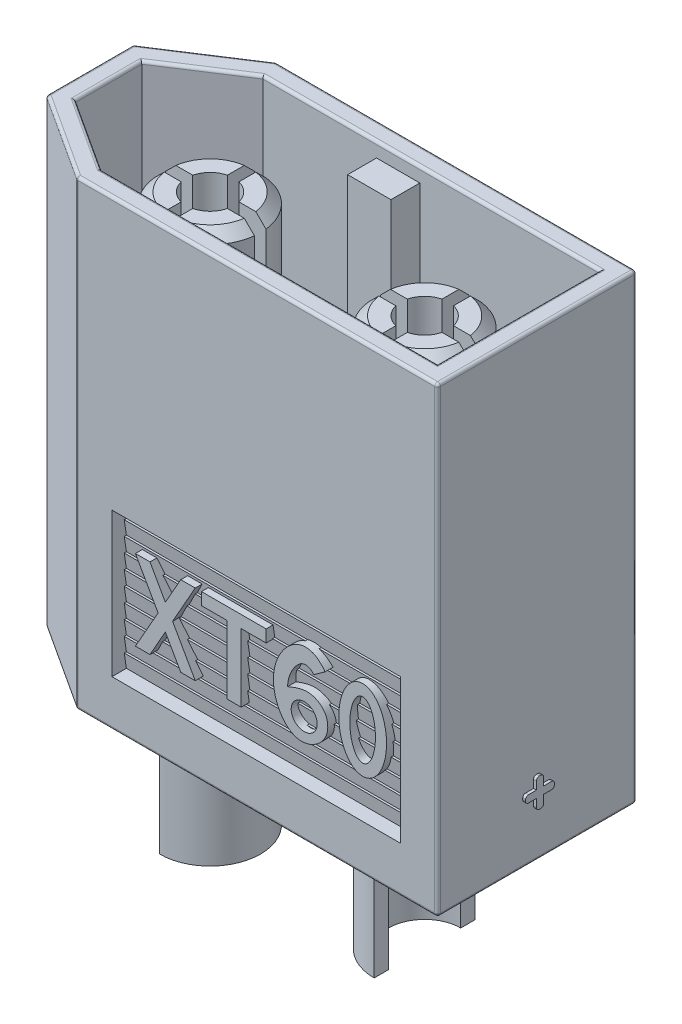
SolidWorks part; units mm, degrees
material "PMMA"
ref_plane "Front Plane" through (0, 0, 0) normal (0, 0, 1) x (1, 0, 0)
ref_plane "Top Plane" through (0, 0, 0) normal (0, 1, 0) x (1, 0, 0)
ref_plane "Right Plane" through (0, 0, 0) normal (1, 0, 0) x (0, 0, -1)
sketch "Sketch1" plane through (0, 0, 0) normal (0, 1, 0) x (1, 0, 0)
  line L1 (-158.75, 87.63) -> (158.75, 87.63)
  line L3 (-158.75, -87.63) -> (158.75, -87.63)
  line L4 (158.75, 87.63) -> (158.75, -87.63)
  line L5 (-158.75, 87.63) -> (158.75, -87.63) construction
  line L6 (-158.75, -87.63) -> (158.75, 87.63) construction
  line L7 (-234.95, 38.1) -> (-234.95, -38.1)
  line L8 (-234.95, 38.1) -> (-158.75, 87.63)
  line L9 (-234.95, -38.1) -> (-158.75, -87.63)
  point P0 (0, 0)
  point P11 (-234.95, 0)
  dimension "D1" = 317.5
  dimension "D2" = 175.26
  dimension "D3" = 76.2
  dimension "D4" = 76.2
  dimension "D5" = 76.2
extrude "Boss-Extrude1" add sketch "Sketch1" along normal blind 406.4
sketch "Sketch4" plane through (0, 406.4, 0) normal (0, 1, 0) x (1, 0, 0)
  line L12 (142.24, -71.12) -> (142.24, 71.12)
  line L13 (142.24, 71.12) -> (-153.8558, 71.12)
  line L14 (-153.8558, 71.12) -> (-218.44, 29.1403)
  line L15 (-218.44, 29.1403) -> (-218.44, -29.1403)
  line L16 (-218.44, -29.1403) -> (-153.8558, -71.12)
  line L17 (-153.8558, -71.12) -> (142.24, -71.12)
  line L18 (142.24, -71.12) -> (142.24, 71.12)
  line L19 (142.24, 71.12) -> (-153.8558, 71.12)
  line L20 (-153.8558, 71.12) -> (-218.44, 29.1403)
  line L21 (-218.44, 29.1403) -> (-218.44, -29.1403)
  line L22 (-218.44, -29.1403) -> (-153.8558, -71.12)
  line L23 (-153.8558, -71.12) -> (142.24, -71.12)
  dimension "D1" = 16.51
extrude "Cut-Extrude2" cut sketch "Sketch4" against normal blind 215.9
sketch "Sketch5" plane through (0, 0, 0) normal (0, -1, 0) x (1, 0, 0)
  circle A0 centre (-129.1768, 0) radius 69.85
  circle A1 centre (59.7244, 0) radius 69.85
extrude "Cut-Extrude3" cut sketch "Sketch5" against normal blind 76.2
sketch "Sketch6" plane through (0, 76.2, 0) normal (0, -1, 0) x (1, 0, 0)
  circle A0 centre (-129.1768, 0) radius 47.625
  circle A1 centre (59.7244, 0) radius 47.625
extrude "Boss-Extrude2" add sketch "Sketch6" along normal blind 2.54 and the other way blind 121.92 contours A0 | A1
sketch "Sketch7" plane through (0, 73.66, 0) normal (0, -1, 0) x (1, 0, 0)
  circle A0 centre (-129.1768, 0) radius 44.45
  circle A1 centre (59.7244, 0) radius 44.45
extrude "Boss-Extrude3" add sketch "Sketch7" along normal blind 190.5 and the other way blind 292.1
chamfer "Chamfer2" distance 6.35 angle 50 2 edges at (-129.1768, 198.12, -47.625) (59.7244, 198.12, -47.625) first distance on face at (-129.1768, 198.12, -44.45) first distance on face at (59.7244, 198.12, -44.45)
sketch "Sketch8" plane through (0, -116.84, 0) normal (0, -1, 0) x (1, 0, 0)
  line L0 (59.7244, -44.45) -> (59.7244, -31.75)
  line L1 (-129.1768, -44.45) -> (-129.1768, -31.75)
  line L2 (59.7244, 31.75) -> (59.7244, 44.45)
  line L3 (-129.1768, 31.75) -> (-129.1768, 44.45)
  arc A0 (59.7244, 31.75) -> (59.7244, -31.75) centre (59.7244, 0) ccw
  circle A1 centre (59.7244, 0) radius 44.45
  arc A2 (59.7244, -44.45) -> (59.7244, 44.45) centre (59.7244, 0) ccw
  circle A3 centre (-129.1768, 0) radius 44.45
  arc A4 (-129.1768, 44.45) -> (-129.1768, -44.45) centre (-129.1768, 0) ccw
  arc A5 (-129.1768, -31.75) -> (-129.1768, 31.75) centre (-129.1768, 0) ccw
  point P11 (59.7244, 0)
  point P14 (-129.1768, 0)
  dimension "D1" = 0
  dimension "D2" = 0
extrude "Cut-Extrude4" cut sketch "Sketch8" against normal blind 95.25
sketch "Sketch9" plane through (0, -21.59, 0) normal (0, -1, 0) x (1, 0, 0)
  circle A0 centre (-129.1768, 0) radius 31.75
  circle A1 centre (59.7244, 0) radius 31.75
extrude "Cut-Extrude5" cut sketch "Sketch9" against normal blind 170.942
sketch "Sketch10" plane through (0, 365.76, 0) normal (0, 1, 0) x (1, 0, 0)
  circle A0 centre (-129.1768, 0) radius 20.955
  circle A1 centre (59.7244, 0) radius 20.955
extrude "Cut-Extrude6" cut sketch "Sketch10" against normal blind 610.362
fillet "Chamfer3" radius 8.89 1 edges at (-129.1768, 365.76, -44.45) type face fillet profile chamfer first side face at (-129.1768, 194.3362, -44.45) second side face at (-129.1768, 365.76, 20.955)
fillet "Chamfer4" radius 8.89 1 edges at (59.7244, 365.76, -44.45) type face fillet profile chamfer first side face at (59.7244, 194.3362, -44.45) second side face at (59.7244, 365.76, 20.955)
sketch "Sketch12" plane through (0, 365.76, 0) normal (0, 1, 0) x (1, 0, 0)
  line L0 (64.8044, -5.08) -> (120.481, -5.08)
  line L1 (-188.1008, 5.08) -> (-134.2568, 5.08)
  line L2 (-188.1008, 5.08) -> (-188.1008, -5.08)
  line L3 (-188.1008, -5.08) -> (-134.2568, -5.08)
  line L4 (-70.2527, 5.08) -> (-70.2527, -5.08)
  line L5 (54.6444, -5.08) -> (54.6444, -61.0793)
  line L6 (64.8044, 5.08) -> (120.481, 5.08)
  line L7 (-134.2568, 61.0793) -> (-124.0968, 61.0793)
  line L8 (-134.2568, 61.0793) -> (-134.2568, 5.08)
  line L9 (-134.2568, -61.0793) -> (-124.0968, -61.0793)
  line L10 (-124.0968, 61.0793) -> (-124.0968, 5.08)
  line L11 (64.8044, -5.08) -> (64.8044, -61.0793)
  line L12 (-124.0968, -5.08) -> (-70.2527, -5.08)
  line L13 (54.6444, 61.0793) -> (64.8044, 61.0793)
  line L14 (54.6444, 61.0793) -> (54.6444, 5.08)
  line L15 (54.6444, -61.0793) -> (64.8044, -61.0793)
  line L16 (64.8044, 61.0793) -> (64.8044, 5.08)
  line L17 (-134.2568, -5.08) -> (-134.2568, -61.0793)
  line L18 (-124.0968, 5.08) -> (-70.2527, 5.08)
  line L19 (-1.0323, 5.08) -> (54.6444, 5.08)
  line L20 (-1.0323, 5.08) -> (-1.0323, -5.08)
  line L21 (-1.0323, -5.08) -> (54.6444, -5.08)
  line L22 (120.481, 5.08) -> (120.481, -5.08)
  line L23 (-124.0968, -5.08) -> (-124.0968, -61.0793)
  point P0 (-129.1768, 0)
  point P6 (-129.1768, 0)
  point P11 (59.7244, 0)
  point P17 (59.7244, 0)
  dimension "D1" = 10.16
  dimension "D2" = 10.16
  dimension "D3" = 10.16
  dimension "D4" = 10.16
extrude "Cut-Extrude7" cut sketch "Sketch12" against normal blind 127
sketch "Sketch13" plane through (0, 190.5, 0) normal (0, 1, 0) x (1, 0, 0)
  line L0 (-81.5518, 0) -> (12.0994, 0)
  line L1 (-153.8558, -71.12) -> (142.24, -71.12) construction
  line L2 (-53.7762, 71.12) -> (-15.6762, 71.12)
  line L3 (-53.7762, 71.12) -> (-53.7762, -71.12)
  line L4 (-53.7762, -71.12) -> (-15.6762, -71.12)
  line L5 (-15.6762, 71.12) -> (-15.6762, -71.12)
  line L6 (-53.7762, 71.12) -> (-15.6762, -71.12) construction
  line L7 (-53.7762, -71.12) -> (-15.6762, 71.12) construction
  circle A0 centre (-129.1768, 0) radius 47.625 construction
  circle A1 centre (59.7244, 0) radius 47.625 construction
  point P7 (-34.7262, 0)
  dimension "D1" = 38.1
extrude "Cut-Extrude8" cut sketch "Sketch13" against normal blind 43.18 contours L3 L4 L5 L2
sketch "Sketch14" plane through (0, 147.32, 0) normal (0, 1, 0) x (1, 0, 0)
  line L0 (-15.6762, 71.12) -> (-15.6762, -71.12) construction
  line L1 (-53.7762, 71.12) -> (-15.6762, 71.12)
  line L2 (-53.7762, 71.12) -> (-53.7762, 45.72)
  line L3 (-53.7762, 45.72) -> (-15.6762, 45.72)
  line L4 (-15.6762, 71.12) -> (-15.6762, 45.72)
  dimension "D1" = 25.4
extrude "Boss-Extrude4" add sketch "Sketch14" along normal blind 246.38
fillet "Fillet1" radius 2.54 24 edges at (158.75, 406.4, 0) (142.24, 406.4, 0) (-5.8079, 406.4, -71.12) (-186.1479, 406.4, -50.1301) (-218.44, 406.4, 0) (-186.1479, 406.4, 50.1301) (-5.8079, 406.4, 71.12) (0, 406.4, 87.63) (0, 406.4, -87.63) (-196.85, 406.4, -62.865) (-234.95, 406.4, 0) (-196.85, 406.4, 62.865) (-196.85, 0, -62.865) (-234.95, 0, 0) (-196.85, 0, 62.865) (0, 0, 87.63) (158.75, 0, 0) (0, 0, -87.63) (158.75, 203.2, 87.63) (-158.75, 203.2, 87.63) (-234.95, 203.2, 38.1) (-234.95, 203.2, -38.1) (-158.75, 203.2, -87.63) (158.75, 203.2, -87.63)
sketch "Sketch15" plane through (158.75, 0, 0) normal (1, 0, 0) x (0, 0, -1)
  line L0 (3.175, 56.515) -> (12.7, 56.515)
  line L2 (-3.175, 50.165) -> (-3.175, 40.64)
  line L3 (-12.7, 56.515) -> (-3.175, 56.515)
  line L4 (-12.7, 56.515) -> (-12.7, 50.165)
  line L5 (-12.7, 50.165) -> (-3.175, 50.165)
  line L6 (12.7, 56.515) -> (12.7, 50.165)
  line L7 (3.175, 50.165) -> (3.175, 40.64)
  line L8 (3.175, 50.165) -> (12.7, 50.165)
  line L9 (3.175, 66.04) -> (-3.175, 66.04)
  line L10 (3.175, 66.04) -> (3.175, 56.515)
  line L11 (3.175, 40.64) -> (-3.175, 40.64)
  line L12 (-3.175, 66.04) -> (-3.175, 56.515)
extrude "Boss-Extrude5" add sketch "Sketch15" along normal blind 2.54
fillet "Fillet3" radius 2.54 8 edges at (160.02, 66.04, 3.175) (160.02, 56.515, 12.7) (160.02, 50.165, 12.7) (160.02, 40.64, 3.175) (160.02, 40.64, -3.175) (160.02, 50.165, -12.7) (160.02, 56.515, -12.7) (160.02, 66.04, -3.175)
sketch "Sketch16" plane through (-234.95, 0, 0) normal (-1, 0, 0) x (0, 0, 1)
  line L3 (-12.7, 56.515) -> (12.7, 56.515)
  line L4 (-12.7, 56.515) -> (-12.7, 50.165)
  line L5 (-12.7, 50.165) -> (12.7, 50.165)
  line L6 (12.7, 56.515) -> (12.7, 50.165)
  line L7 (-12.7, 56.515) -> (12.7, 50.165) construction
  line L8 (-12.7, 50.165) -> (12.7, 56.515) construction
extrude "Boss-Extrude6" add sketch "Sketch16" along normal blind 2.54
fillet "Fillet4" radius 2.54 4 edges at (-236.22, 50.165, -12.7) (-236.22, 56.515, -12.7) (-236.22, 50.165, 12.7) (-236.22, 56.515, 12.7)
sketch "Sketch17" plane through (0, 0, -87.63) normal (0, 0, -1) x (-1, 0, 0)
  line L0 (0.8935, 2.54) -> (0.8935, 104.14)
  line L1 (-156.21, 2.54) -> (157.997, 2.54) construction
  line L3 (127.8935, 167.64) -> (-126.1065, 167.64)
  line L4 (127.8935, 167.64) -> (127.8935, 40.64)
  line L5 (127.8935, 40.64) -> (-126.1065, 40.64)
  line L6 (-126.1065, 167.64) -> (-126.1065, 40.64)
  line L7 (127.8935, 167.64) -> (-126.1065, 40.64) construction
  line L8 (127.8935, 40.64) -> (-126.1065, 167.64) construction
  dimension "D1" = 101.6
  dimension "D2" = 254
  dimension "D3" = 127
extrude "Cut-Extrude9" cut sketch "Sketch17" against normal blind 12.7 contours L3 L6 L5 L4 region at (-125.0537, 104.14, -87.63)
sketch "Sketch18" plane through (0, 0, 87.63) normal (0, 0, 1) x (1, 0, 0)
  line L4 (126.1065, 167.64) -> (-127.8935, 167.64)
  line L5 (126.1065, 40.64) -> (126.1065, 167.64)
  line L6 (-127.8935, 40.64) -> (126.1065, 40.64)
  line L7 (-127.8935, 167.64) -> (-127.8935, 40.64)
  line L8 (126.1065, 167.64) -> (-127.8935, 167.64)
  line L9 (126.1065, 40.64) -> (126.1065, 167.64)
  line L10 (-127.8935, 40.64) -> (126.1065, 40.64)
  line L11 (-127.8935, 167.64) -> (-127.8935, 40.64)
  dimension "D1" = 0
extrude "Cut-Extrude10" cut sketch "Sketch18" against normal blind 12.7
sketch "Sketch20" plane through (126.1065, 0, 0) normal (-1, 0, 0) x (0, 0, 1)
  line L0 (-76.835, 167.64) -> (-74.93, 154.94)
  line L1 (-74.93, 167.64) -> (-76.835, 167.64)
  line L5 (-74.93, 154.94) -> (-76.835, 154.94)
  line L6 (-76.835, 154.94) -> (-74.93, 142.24)
  line L7 (-74.93, 142.24) -> (-76.835, 142.24)
  line L8 (-76.835, 142.24) -> (-74.93, 129.54)
  line L9 (-74.93, 129.54) -> (-76.835, 129.54)
  line L10 (-76.835, 129.54) -> (-74.93, 116.84)
  line L11 (-74.93, 116.84) -> (-76.835, 116.84)
  line L12 (-76.835, 116.84) -> (-74.93, 104.14)
  line L13 (-74.93, 104.14) -> (-76.835, 104.14)
  line L14 (-76.835, 104.14) -> (-74.93, 91.44)
  line L15 (-74.93, 91.44) -> (-76.835, 91.44)
  line L16 (-76.835, 91.44) -> (-74.93, 78.74)
  line L17 (-74.93, 78.74) -> (-76.835, 78.74)
  line L18 (-76.835, 78.74) -> (-74.93, 66.04)
  line L19 (-74.93, 66.04) -> (-76.835, 66.04)
  line L20 (-76.835, 66.04) -> (-74.93, 53.34)
  line L21 (-74.93, 53.34) -> (-76.835, 53.34)
  line L22 (-76.835, 53.34) -> (-74.93, 40.64)
  line L24 (-74.93, 167.64) -> (-73.0547, 167.64)
  line L25 (-73.0547, 167.64) -> (-73.0547, 40.64)
  line L26 (-73.0547, 40.64) -> (-74.93, 40.64)
  dimension "D1" = 10
extrude "Boss-Extrude8" add sketch "Sketch20" along normal blind 254
sketch "Sketch24" plane through (0, 0, 74.93) normal (0, 0, 1) x (1, 0, 0)
  line L3 (-112.3337, 69.136) -> (-99.5117, 69.136)
  line L8 (-59.6881, 69.136) -> (-72.3956, 69.136)
  line L9 (-59.6881, 139.7869) -> (-72.3956, 139.7869)
  line L10 (-112.3337, 139.7869) -> (-99.5117, 139.7869)
  line L11 (-99.5117, 139.7869) -> (-85.9731, 115.7681)
  line L12 (-72.3956, 139.7869) -> (-85.9731, 115.7681)
  line L13 (-112.3337, 139.7869) -> (-92.3647, 104.4615)
  line L14 (-59.6881, 139.7869) -> (-79.5999, 104.4615)
  line L15 (-92.3647, 104.4615) -> (-112.3337, 69.136)
  line L16 (-79.5999, 104.4615) -> (-59.6881, 69.136)
  line L18 (-85.9731, 93.1548) -> (-99.5117, 69.136)
  line L19 (-85.9731, 93.1548) -> (-72.3956, 69.136)
  line L20 (-19.2107, 129.0815) -> (2.744, 129.0815)
  line L21 (-19.2107, 139.8309) -> (-31.8277, 139.8309)
  line L22 (-19.2107, 129.0815) -> (-19.2107, 69.18)
  line L23 (-19.2107, 69.18) -> (-31.8277, 69.18)
  line L24 (-31.8277, 129.0815) -> (-31.8277, 69.18)
  line L25 (44.665, 125.9321) -> (54.5941, 133.0073)
  line L27 (-54.2126, 139.8309) -> (2.744, 139.8309)
  line L28 (-54.2126, 139.8309) -> (-54.2126, 129.0815)
  line L29 (-54.2126, 129.0815) -> (-31.8277, 129.0815)
  line L30 (2.744, 139.8309) -> (2.744, 129.0815)
  circle A0 centre (36.2346, 89.7538) radius 11.4519
  ellipse E0 centre (87.7023, 105.3338) end of major axis (87.7023, 69.9643) minor radius 21.0247
  ellipse E1 centre (87.7023, 105.3338) end of major axis (87.7023, 80.0414) minor radius 11.2698
  spline S2 degree 3 poles (54.5941, 133.0073) (36.5453, 158.3364) (-7.5592, 116.0653) (25.4379, 59.9073) (57.7026, 79.0859) (57.8368, 102.2901) (40.1612, 112.982) (28.1928, 107.9257) (21.6829, 105.2817) (21.6192, 105.2555) knots 0 0 0 0 0.346903 0.566821 0.697461 0.793699 0.867755 0.974591 0.975653 0.975653 0.975653 0.975653
  spline S3 degree 3 poles (44.665, 125.9321) (37.8345, 133.7755) (25.8368, 123.8865) (21.7671, 111.0708) (21.6192, 105.2555) knots 0 0 0 0 0.190849 0.355801 0.355801 0.355801 0.355801
  point P6 (-86.0109, 104.4615)
  point P19 (-25.5192, 104.4615)
extrude "Boss-Extrude9" add sketch "Sketch24" along normal blind 7.62 contours L18 L19 L8 L16 L14 L9 L12 L11 L10 L13 L15 L3 | L30 L27 L21 L28 L29 L24 L23 L22 L20 | S3 L25 S2 A0 | E0 E1 region at (-86.015, 104.4615, 74.93) region at (-25.6155, 114.9404, 74.93) region at (31.1425, 105.8846, 74.93) region at (87.6546, 139.8803, 74.93)
mirror "Mirror2" about plane through (0, 0, 0) normal (0, 0, 1) of "Boss-Extrude8"
ref_plane "Plane1" through (0, 0, -74.93) normal (0, 0, -1) x (-1, 0, 0)
sketch "Sketch26" plane through (0, 0, -74.93) normal (0, 0, -1) x (-1, 0, 0)
  line L0 (-106.5636, 67.9422) -> (-93.7416, 67.9422)
  line L1 (-53.9181, 67.9422) -> (-66.6255, 67.9422)
  line L2 (-53.9181, 138.5931) -> (-66.6255, 138.5931)
  line L3 (-106.5636, 138.5931) -> (-93.7416, 138.5931)
  line L4 (-93.7416, 138.5931) -> (-80.2031, 114.5743)
  line L5 (-66.6255, 138.5931) -> (-80.2031, 114.5743)
  line L6 (-106.5636, 138.5931) -> (-86.5946, 103.2676)
  line L7 (-53.9181, 138.5931) -> (-73.8299, 103.2676)
  line L8 (-86.5946, 103.2676) -> (-106.5636, 67.9422)
  line L9 (-73.8299, 103.2676) -> (-53.9181, 67.9422)
  line L10 (-80.2031, 91.961) -> (-93.7416, 67.9422)
  line L11 (-80.2031, 91.961) -> (-66.6255, 67.9422)
  line L12 (-13.4406, 127.8876) -> (8.5141, 127.8876)
  line L13 (-13.4406, 138.6371) -> (-26.0576, 138.6371)
  line L14 (-13.4406, 127.8876) -> (-13.4406, 67.9862)
  line L15 (-13.4406, 67.9862) -> (-26.0576, 67.9862)
  line L16 (-26.0576, 127.8876) -> (-26.0576, 67.9862)
  line L17 (50.4351, 124.7383) -> (60.3642, 131.8134)
  line L18 (-48.4425, 138.6371) -> (8.5141, 138.6371)
  line L19 (-48.4425, 138.6371) -> (-48.4425, 127.8876)
  line L20 (-48.4425, 127.8876) -> (-26.0576, 127.8876)
  line L21 (8.5141, 138.6371) -> (8.5141, 127.8876)
  circle A0 centre (42.0047, 88.56) radius 11.4519
  ellipse E0 centre (93.4724, 104.14) end of major axis (93.4724, 68.7705) minor radius 21.0247
  ellipse E1 centre (93.4724, 104.14) end of major axis (93.4724, 78.8476) minor radius 11.2698
  spline S0 degree 3 poles (60.3642, 131.8134) (42.3154, 157.1426) (-1.7892, 114.8715) (31.208, 58.7135) (63.4727, 77.8921) (63.6069, 101.0963) (45.9313, 111.7882) (33.9629, 106.7318) (27.453, 104.0879) (27.3893, 104.0617) knots 0 0 0 0 0.346903 0.566821 0.697461 0.793699 0.867755 0.974591 0.975653 0.975653 0.975653 0.975653
  spline S1 degree 3 poles (50.4351, 124.7383) (43.6046, 132.5817) (31.6068, 122.6926) (27.5371, 109.877) (27.3893, 104.0617) knots 0 0 0 0 0.190849 0.355801 0.355801 0.355801 0.355801
  point P0 (-80.2408, 103.2676)
  point P13 (-19.7491, 103.2676)
extrude "Boss-Extrude10" add sketch "Sketch26" along normal blind 7.62 contours L21 L18 L13 L19 L20 L16 L15 L14 L12 | S1 L17 S0 A0 | E0 E1 | L8 L0 L10 L11 L1 L9 L7 L2 L5 L4 L3 L6 region at (19.8454, 113.7466, -74.93) region at (-36.9126, 104.6908, -74.93) region at (-93.4247, 138.6865, -74.93)
